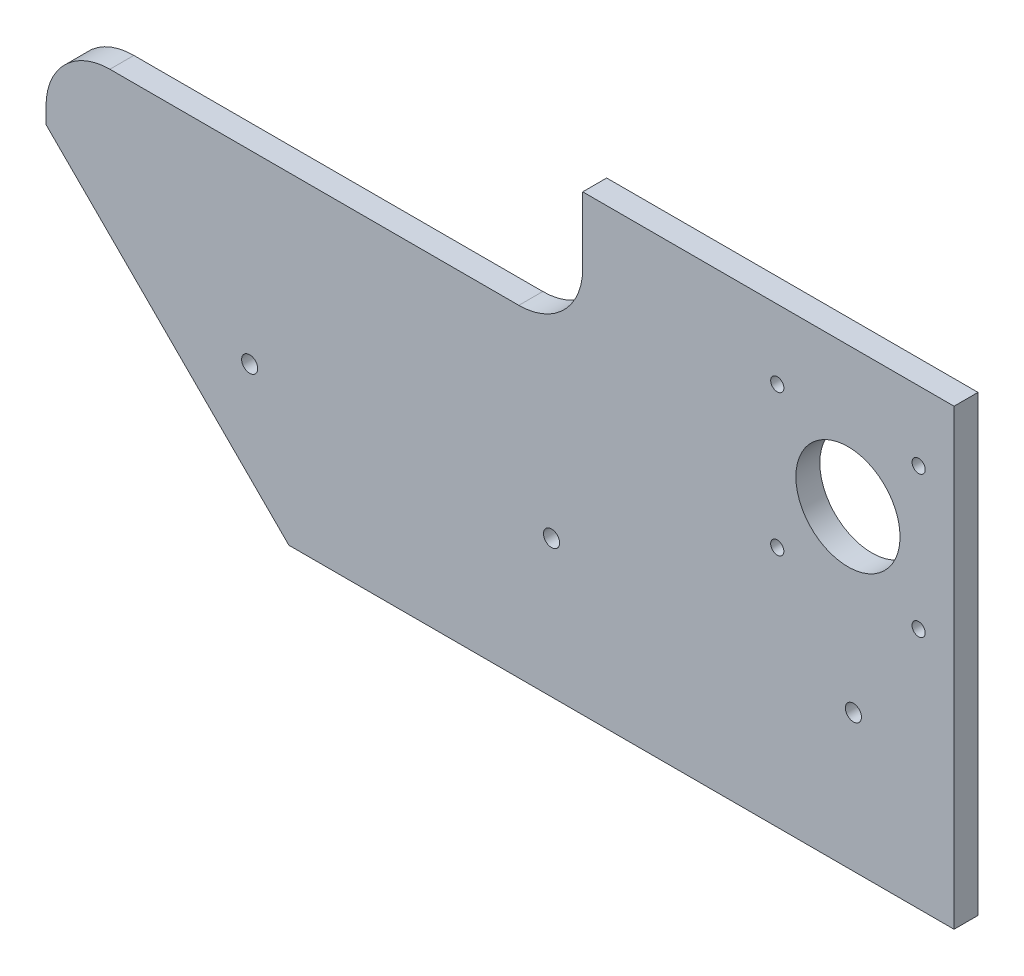
SolidWorks part; units mm, degrees
ref_plane "Front Plane" through (0, 0, 0) normal (0, 0, 1) x (1, 0, 0)
ref_plane "Top Plane" through (0, 0, 0) normal (0, 1, 0) x (1, 0, 0)
ref_plane "Right Plane" through (0, 0, 0) normal (1, 0, 0) x (0, 0, -1)
sketch "Sketch1" plane through (0, 0, 0) normal (0, 0, 1) x (1, 0, 0)
  line L0 (-138.2594, 48.9915) -> (32.2106, -121.4785)
  line L1 (32.2106, -121.4785) -> (222.7106, -121.4785)
  line L2 (-138.2594, 146.2068) -> (-138.2594, 48.9915)
  line L3 (-138.2594, 146.2068) -> (222.7106, 146.2068)
  line L4 (222.7106, -121.4785) -> (222.7106, 146.2068)
  circle A0 centre (180.538, 76.832) radius 20.701
  circle A2 centre (180.538, 76.832) radius 69.85 construction
  circle A3 centre (180.538, 76.832) radius 318.7974 construction
  point P0 (0, 0)
  point P2 (180.538, 76.832)
  dimension "D4" = 198.3105
  dimension "D1" = 45
  dimension "D2" = 267.6854
  dimension "D5" = 245.11
extrude "Boss-Extrude1" add sketch "Sketch1" along normal blind 9.525
sketch "Sketch2" plane through (0, 0, 9.525) normal (0, 0, 1) x (1, 0, 0)
  line L0 (32.2106, -121.4785) -> (222.7106, -121.4785) construction
  line L1 (241.7606, -121.4785) -> (-43.8123, -121.4785)
  line L2 (241.7606, -121.4785) -> (241.7606, -47.5645)
  line L3 (241.7606, -47.5645) -> (-43.8123, -47.5645)
  line L4 (-43.8123, -121.4785) -> (-43.8123, -47.5645)
extrude "Cut-Extrude1" cut sketch "Sketch2" against normal through all contours L3 L4 L1 L2
sketch "Sketch4" plane through (0, 0, 9.525) normal (0, 0, 1) x (1, 0, 0)
  line L1 (-138.2594, 146.2068) -> (-138.2594, 48.9915) construction
  line L3 (-138.2594, 146.2068) -> (75.1006, 146.2068)
  line L4 (-138.2594, 146.2068) -> (-138.2594, 80.7415)
  line L5 (-138.2594, 80.7415) -> (75.1006, 80.7415)
  line L6 (75.1006, 146.2068) -> (75.1006, 80.7415)
extrude "Cut-Extrude2" cut sketch "Sketch4" against normal through all contours L5 L6 L3 L4
fillet "Fillet2" radius 25.4 2 edges at (-138.2594, 80.7415, 4.7625) (75.1006, 80.7415, 4.7625)
hole_wizard "Ø6.4 (6.4) Diameter Hole2" positions "Sketch15" profile "Sketch14" hole size "Ø6.4" standard "Lanco STD" end condition through all
sketch "Sketch15" plane through (0, 0, 0) normal (0, 0, -1) x (-1, 0, 0)
  line L2 (-222.7106, -47.5645) -> (-222.7106, 146.2068) construction
  point P3 (-182.7106, 7.0429)
  point P6 (-62.7106, 7.0429)
  point P9 (57.2894, 7.0429)
  dimension "D1" = 40
  dimension "D2" = 120
  dimension "D3" = 120
sketch "Sketch14" plane through (182.7106, 7.0429, 0) normal (1, 0, 0) x (0, 1, 0)
  line L0 (0, 0) -> (0, 9.525)
  line L1 (0, 9.525) -> (3.2, 9.525)
  line L2 (3.2, 9.525) -> (3.2, 0)
  line L5 (3.2, 0) -> (0, 0)
  line L11 (0, -6.35) -> (0, 107.95) construction
  dimension "Thru Hole Dia." = 6.4
  dimension "Thru Hole Depth" = 9.525
sketch "Sketch16" plane through (222.7106, 0, 0) normal (1, 0, 0) x (0, 0, -1)
  line L0 (0, -47.5645) -> (0, 146.2068) construction
  line L1 (-9.525, 146.2068) -> (0, 146.2068)
  line L2 (-9.525, 146.2068) -> (-9.525, 145.2215)
  line L3 (-9.525, 145.2215) -> (0, 145.2215)
  line L4 (0, 146.2068) -> (0, 145.2215)
extrude "Cut-Extrude3" cut sketch "Sketch16" against normal through all
sketch "Sketch17" plane through (0, 0, 0) normal (0, 0, -1) x (-1, 0, 0)
  line L0 (-222.7106, -47.5645) -> (-222.7106, 145.2215) construction
  line L1 (-75.1006, 145.2215) -> (-222.7106, 145.2215)
  line L2 (-75.1006, 145.2215) -> (-75.1006, 132.5215)
  line L3 (-75.1006, 132.5215) -> (-222.7106, 132.5215)
  line L4 (-222.7106, 145.2215) -> (-222.7106, 132.5215)
  dimension "D1" = 12.7
extrude "Cut-Extrude4" cut sketch "Sketch17" against normal through all
hole_wizard "Tap Drill for M6x0.75 Tap1" positions "Sketch19" profile "Sketch18" hole size "M6x0.75" standard "Lanco STD" end condition through all
sketch "Sketch19" plane through (0, 0, 9.525) normal (0, 0, 1) x (1, 0, 0)
  point P0 (208.638, 104.932)
  point P3 (152.438, 104.932)
  point P6 (152.438, 48.732)
  point P9 (208.638, 48.732)
sketch "Sketch18" plane through (208.638, 104.932, 9.525) normal (1, 0, 0) x (0, -1, 0)
  line L0 (0, 0) -> (0, 9.525)
  line L1 (0, 9.525) -> (2.625, 9.525)
  line L2 (2.625, 9.525) -> (2.625, 0)
  line L5 (2.625, 0) -> (0, 0)
  line L11 (0, -6.35) -> (0, 107.95) construction
  dimension "Thru Hole Dia." = 5.25
  dimension "Thru Hole Depth" = 9.525
